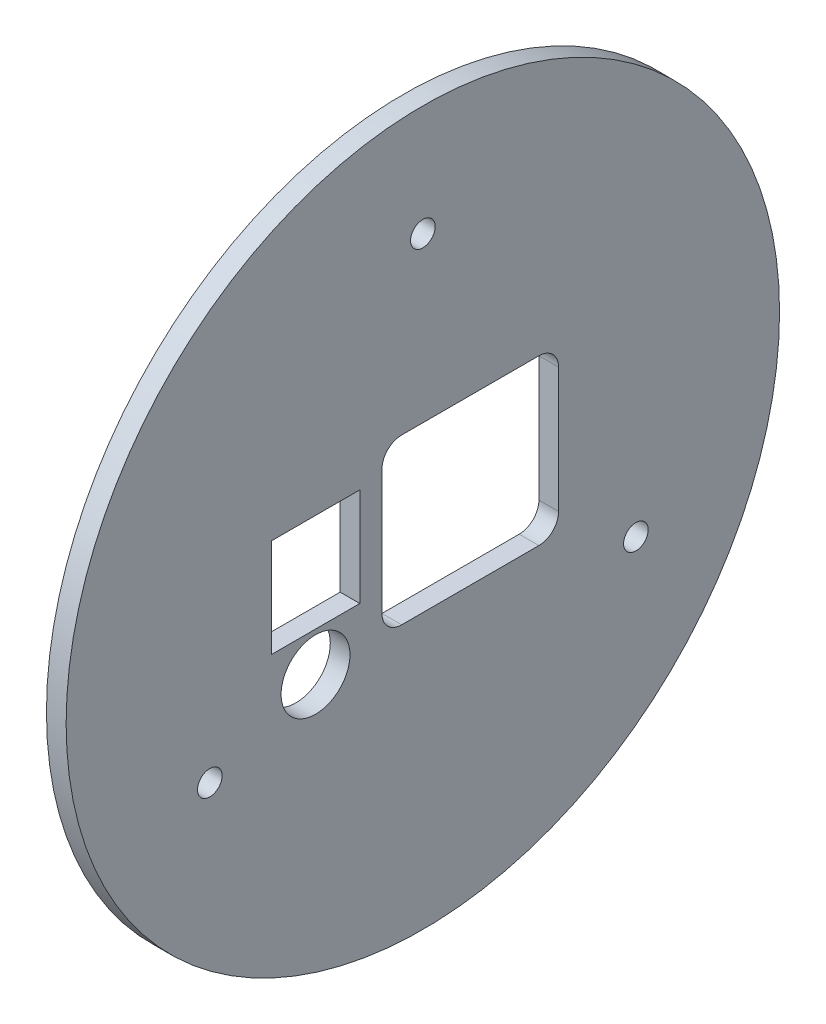
SolidWorks part; units mm, degrees
ref_plane "Front Plane" through (0, 0, 0) normal (0, 0, 1) x (1, 0, 0)
ref_plane "Top Plane" through (0, 0, 0) normal (0, 1, 0) x (1, 0, 0)
ref_plane "Right Plane" through (0, 0, 0) normal (1, 0, 0) x (0, 0, -1)
sketch "Sketch1" plane through (0, 0, 0) normal (1, 0, 0) x (0, 0, -1)
  line L0 (-72.5, 0) -> (72.5, 0) construction
  line L1 (-4.3098, 16.7) -> (23.5902, 16.7)
  line L2 (-8.3098, 12.7) -> (-8.3098, -12.7)
  line L3 (-4.3098, -16.7) -> (23.5902, -16.7)
  line L4 (27.5902, 12.7) -> (27.5902, -12.7)
  line L5 (4.2715, -16.7) -> (-70.5504, -16.7) construction
  line L6 (-21.8098, -16.7) -> (-21.8098, 69.1418) construction
  line L7 (-30.8098, 11.3) -> (-12.8098, 11.3)
  line L8 (-30.8098, 11.3) -> (-30.8098, -8.7)
  line L9 (-30.8098, -8.7) -> (-12.8098, -8.7)
  line L10 (-12.8098, 11.3) -> (-12.8098, -8.7)
  line L11 (0, 72.5) -> (0, -72.5) construction
  circle A0 centre (0, 0) radius 72.5
  circle A1 centre (-21.8098, -16.7) radius 7
  circle A2 centre (0, 50) radius 2.5
  circle A3 centre (43.3013, -25) radius 2.5
  circle A4 centre (-43.3013, -25) radius 2.5
  arc A5 (-4.3098, -16.7) -> (-8.3098, -12.7) centre (-4.3098, -12.7) cw
  arc A6 (23.5902, -16.7) -> (27.5902, -12.7) centre (23.5902, -12.7) ccw
  arc A7 (27.5902, 12.7) -> (23.5902, 16.7) centre (23.5902, 12.7) ccw
  arc A8 (-4.3098, 16.7) -> (-8.3098, 12.7) centre (-4.3098, 12.7) ccw
  point P13 (0, 0)
  point P29 (-8.3098, -16.7)
  point P32 (27.5902, -16.7)
  point P35 (27.5902, 16.7)
  point P38 (-8.3098, 16.7)
  dimension "D1" = 145
  dimension "D2" = 35.9
  dimension "D3" = 5
  dimension "D7" = 14
  dimension "D12" = 4
  dimension "D4" = 50
  dimension "D6" = 33.4
  dimension "D8" = 13.5
  dimension "D9" = 18
  dimension "D10" = 20
  dimension "D11" = 8
  dimension "D5" = 3
extrude "Boss-Extrude1" add sketch "Sketch1" along normal blind 4
